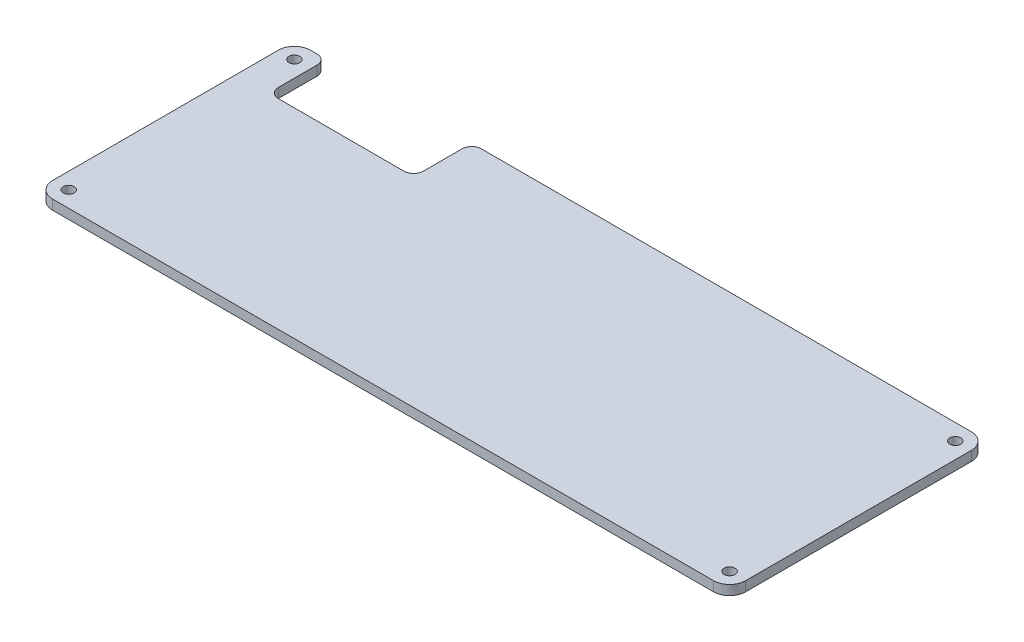
SolidWorks part; units mm, degrees
ref_plane "Front" through (0, 0, 0) normal (0, 0, 1) x (1, 0, 0)
ref_plane "Top" through (0, 0, 0) normal (0, 1, 0) x (1, 0, 0)
ref_plane "Right" through (0, 0, 0) normal (1, 0, 0) x (0, 0, -1)
sketch "Esquisse1" plane through (0, 0, 0) normal (0, 1, 0) x (1, 0, 0)
  line L1 (0, 0) -> (215, 0)
  line L2 (0, 0) -> (0, 80)
  line L3 (0, 80) -> (215, 80)
  line L4 (215, 0) -> (215, 80)
  dimension "D1" = 215
  dimension "D2" = 80
extrude "Boss.-Extru.1" add sketch "Esquisse1" along normal blind 3
fillet "Congé1" radius 5 4 edges at (0, 1.5, -80) (0, 1.5, 0) (215, 1.5, -80) (215, 1.5, 0)
sketch "Esquisse2" plane through (0, 3, 0) normal (0, 1, 0) x (1, 0, 0)
  line L0 (0, 75) -> (0, 5) construction
  line L1 (210, 80) -> (5, 80) construction
  line L2 (5, 0) -> (210, 0) construction
  line L3 (215, 5) -> (215, 75) construction
  line L5 (10, 80) -> (55, 80)
  line L6 (10, 80) -> (10, 62)
  line L7 (10, 62) -> (55, 62)
  line L8 (55, 80) -> (55, 62)
  circle A0 centre (5, 75) radius 1
  circle A1 centre (210, 75) radius 1
  circle A2 centre (210, 5) radius 1
  circle A3 centre (5, 5) radius 1
  dimension "D9" = 2
  dimension "D10" = 2
  dimension "D11" = 2
  dimension "D12" = 2
  dimension "D1" = 5
  dimension "D2" = 5
  dimension "D3" = 5
  dimension "D4" = 5
  dimension "D5" = 5
  dimension "D6" = 5
  dimension "D7" = 5
  dimension "D8" = 5
  dimension "D13" = 10
  dimension "D14" = 45
  dimension "D15" = 18
extrude "Enlèv. mat.-Extru.1" cut sketch "Esquisse2" against normal through all
hole_wizard "Dégagement M31" positions "Esquisse3" profile "Esquisse4" hole size "M3" standard "ISO"
sketch "Esquisse3" plane through (0, 3, 0) normal (0, 1, 0) x (1, 0, 0)
  point P0 (210, 5)
  point P3 (5, 5)
  point P6 (5, 75)
  point P9 (210, 75)
sketch "Esquisse4" plane through (210, 3, -5) normal (1, 0, 0) x (0, 0, 1)
  line L0 (0, 0) -> (0, 11.0215)
  line L1 (0, 11.0215) -> (1.7, 10)
  line L2 (1.7, 10) -> (1.7, 0)
  line L5 (1.7, 0) -> (0, 0)
  line L10 (0, 11.0215) -> (-1.7, 10) construction
  line L11 (0, -6.35) -> (0, 107.95) construction
  dimension "Diamètre du perçage" = 3.4
  dimension "Profondeur du perçage" = 10
  dimension "Angle de pointe" = 118
fillet "Congé2" radius 3 4 edges at (55, 1.5, -62) (55, 1.5, -80) (10, 1.5, -80) (10, 1.5, -62)
